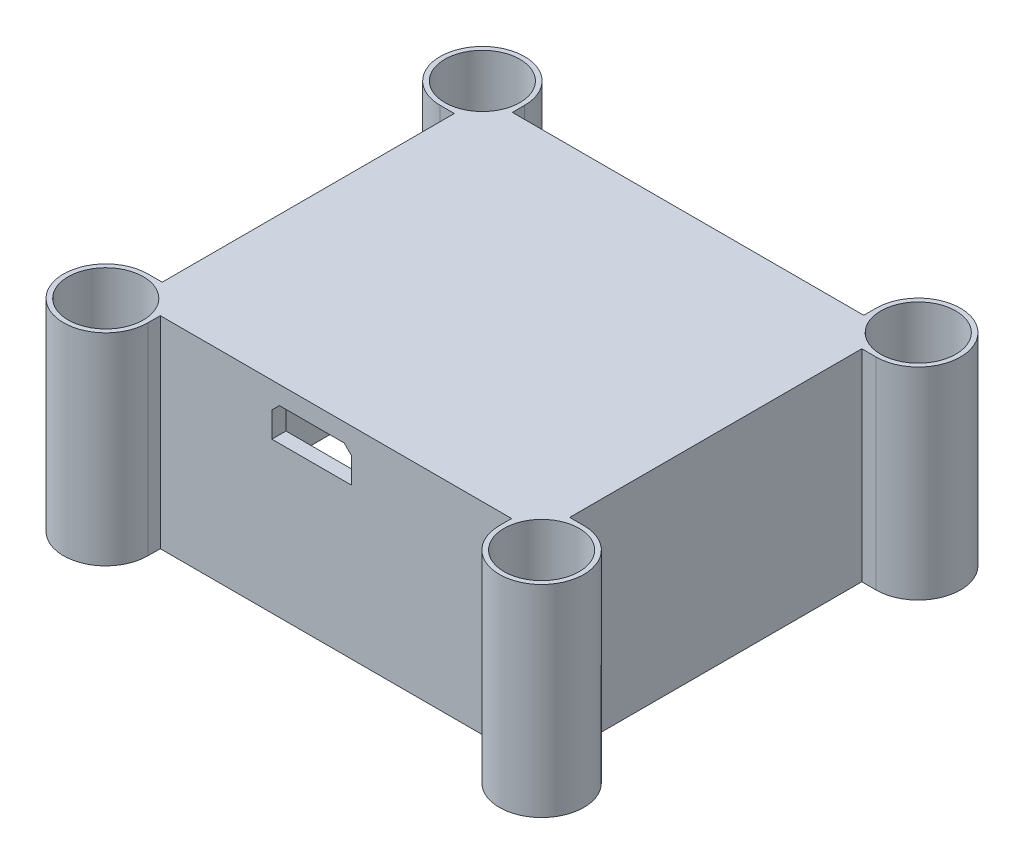
SolidWorks part; units mm, degrees
ref_plane "Front Plane" through (0, 0, 0) normal (0, 0, 1) x (1, 0, 0)
ref_plane "Top Plane" through (0, 0, 0) normal (0, 1, 0) x (1, 0, 0)
ref_plane "Right Plane" through (0, 0, 0) normal (1, 0, 0) x (0, 0, -1)
sketch "Sketch1" plane through (0, 0, 0) normal (0, 1, 0) x (1, 0, 0)
  line L0 (-20.2, 17.25) -> (-21.7, 17.25) construction
  line L1 (-20.2, 17.25) -> (20.2, 17.25)
  line L2 (-20.2, 17.25) -> (-20.2, -17.25)
  line L3 (-20.2, -17.25) -> (20.2, -17.25)
  line L4 (20.2, 17.25) -> (20.2, -17.25)
  line L5 (-20.2, 17.25) -> (20.2, -17.25) construction
  line L6 (-20.2, -17.25) -> (20.2, 17.25) construction
  line L7 (-20.2, 17.25) -> (20.2, 17.25)
  line L8 (-20.2, 17.25) -> (-20.2, 27.25)
  line L9 (-20.2, 27.25) -> (20.2, 27.25)
  line L10 (20.2, 17.25) -> (20.2, 27.25)
  line L11 (21.7, -18.75) -> (-21.7, -18.75)
  line L12 (21.7, -18.75) -> (21.7, 18.75)
  line L13 (21.7, 18.75) -> (-21.7, 18.75)
  line L14 (-21.7, -18.75) -> (-21.7, 18.75)
  line L15 (21.7, -18.75) -> (-21.7, 18.75) construction
  line L16 (21.7, 18.75) -> (-21.7, -18.75) construction
  line L17 (-20.2, 17.25) -> (-20.2, 18.75) construction
  line L18 (-23.2133, 15.5576) -> (-21.7, 15.5576)
  line L19 (-18.7133, 20.0576) -> (-18.7133, 18.75)
  line L20 (0, 18.75) -> (0, -18.75) construction
  line L21 (-21.7, 0) -> (21.7, 0) construction
  line L22 (18.7133, 20.0576) -> (18.7133, 18.75)
  line L23 (23.2133, 15.5576) -> (21.7, 15.5576)
  line L24 (18.7133, -20.0576) -> (18.7133, -18.75)
  line L25 (23.2133, -15.5576) -> (21.7, -15.5576)
  line L26 (-18.7133, -20.0576) -> (-18.7133, -18.75)
  line L27 (-23.2133, -15.5576) -> (-21.7, -15.5576)
  circle A0 centre (-23.2133, 20.0576) radius 2
  circle A1 centre (-23.2133, 20.0576) radius 4.5
  circle A2 centre (23.2133, 20.0576) radius 4.5
  circle A3 centre (23.2133, 20.0576) radius 2
  circle A4 centre (-23.2133, -20.0576) radius 2
  circle A5 centre (23.2133, -20.0576) radius 2
  circle A6 centre (23.2133, -20.0576) radius 4.5
  circle A7 centre (-23.2133, -20.0576) radius 4.5
  point P0 (0, 0)
  point P9 (0, 0)
  dimension "D5" = 4
  dimension "D6" = 9
  dimension "D1" = 40.4
  dimension "D2" = 34.5
  dimension "D3" = 10
  dimension "D4" = 1.5
extrude "Boss-Extrude1" add sketch "Sketch1" along normal blind 20 contours A7 L11 A4 L14 | L27 A7 L14 | A7 L14 L11 L3 L2 | L11 A7 L26 | L3 A7 L11 A6 | L14 A7 L2 A1 | A1 L14 A0 L13 L8 | L13 A1 L8 | L14 A1 L2 L8 L13 | L1 A1 L13 L8 | A1 L18 L14 | A1 L13 L19 | L7 A2 L13 A1 | L13 A3 L12 A2 L10 | L13 A2 L22 | A2 L1 L10 L13 | A2 L12 L13 L10 L4 | L23 A2 L12 | A6 L12 A2 L4 | A2 L13 L10 | L12 A6 L4 L3 L11 | A6 L25 L12 | A6 L12 A5 L11 | A6 L11 L24 region at (-19.6937, 0, -18.1019) region at (-20.9935, 0, -17.4625) region at (0, 0, -17.9949) region at (-20.9432, 0, 0) region at (-20.95, 0, -18.8672) region at (-19.558, 0, -20.6683) region at (19.6937, 0, -18.1019) region at (-18.7714, 0, -19.0755) region at (-20.6382, 0, 17.6373) region at (-22.0761, 0, -15.6358) region at (20.9935, 0, -17.4625) region at (19.558, 0, -20.6683) region at (18.7714, 0, -19.0755) region at (20.9432, 0, 0) region at (0, 0, 17.9949) region at (-22.0761, 0, 15.6358) region at (-21.8273, 0, 17.2848) region at (20.3172, 0, -21.0749) region at (20.6382, 0, 17.6373) region at (22.0761, 0, -15.6358) region at (-18.7714, 0, 19.0755) region at (22.4671, 0, 15.749) region at (22.0761, 0, 15.6358) region at (18.7714, 0, 19.0755)
sketch "Sketch2" plane through (0, 20, 0) normal (0, 1, 0) x (1, 0, 0)
  line L12 (-21.7, 15.5576) -> (-21.7, -15.5576)
  line L13 (-21.7, -15.5576) -> (-23.2133, -15.5576)
  line L14 (-18.7133, -20.0576) -> (-18.7133, -18.75)
  line L15 (-18.7133, -18.75) -> (18.7133, -18.75)
  line L16 (18.7133, -18.75) -> (18.7133, -20.0576)
  line L17 (23.2133, -15.5576) -> (21.7, -15.5576)
  line L18 (21.7, -15.5576) -> (21.7, 15.5576)
  line L19 (21.7, 15.5576) -> (23.2133, 15.5576)
  line L20 (18.7133, 20.0576) -> (18.7133, 18.75)
  line L21 (18.7133, 18.75) -> (-18.7133, 18.75)
  line L22 (-18.7133, 18.75) -> (-18.7133, 20.0576)
  line L23 (-23.2133, 15.5576) -> (-21.7, 15.5576)
  line L24 (-21.7, 15.5576) -> (-21.7, -15.5576)
  line L25 (-21.7, -15.5576) -> (-23.2133, -15.5576)
  line L26 (-18.7133, -20.0576) -> (-18.7133, -18.75)
  line L27 (-18.7133, -18.75) -> (18.7133, -18.75)
  line L28 (18.7133, -18.75) -> (18.7133, -20.0576)
  line L29 (23.2133, -15.5576) -> (21.7, -15.5576)
  line L30 (21.7, -15.5576) -> (21.7, 15.5576)
  line L31 (21.7, 15.5576) -> (23.2133, 15.5576)
  line L32 (18.7133, 20.0576) -> (18.7133, 18.75)
  line L33 (18.7133, 18.75) -> (-18.7133, 18.75)
  line L34 (-18.7133, 18.75) -> (-18.7133, 20.0576)
  line L35 (-23.2133, 15.5576) -> (-21.7, 15.5576)
  circle A0 centre (23.2133, -20.0576) radius 2 construction
  circle A1 centre (23.2133, 20.0576) radius 2 construction
  circle A2 centre (-23.2133, 20.0576) radius 2 construction
  circle A3 centre (-23.2133, -20.0576) radius 2 construction
  arc A4 (-23.2133, -15.5576) -> (-18.7133, -20.0576) centre (-23.2133, -20.0576) ccw
  arc A5 (18.7133, -20.0576) -> (23.2133, -15.5576) centre (23.2133, -20.0576) ccw
  arc A6 (23.2133, 15.5576) -> (18.7133, 20.0576) centre (23.2133, 20.0576) ccw
  arc A7 (-18.7133, 20.0576) -> (-23.2133, 15.5576) centre (-23.2133, 20.0576) ccw
  arc A8 (-23.2133, -15.5576) -> (-18.7133, -20.0576) centre (-23.2133, -20.0576) ccw
  arc A9 (18.7133, -20.0576) -> (23.2133, -15.5576) centre (23.2133, -20.0576) ccw
  arc A10 (23.2133, 15.5576) -> (18.7133, 20.0576) centre (23.2133, 20.0576) ccw
  arc A11 (-18.7133, 20.0576) -> (-23.2133, 15.5576) centre (-23.2133, 20.0576) ccw
  circle A12 centre (23.2133, -20.0576) radius 2
  circle A13 centre (23.2133, 20.0576) radius 2
  circle A14 centre (-23.2133, 20.0576) radius 2
  circle A15 centre (-23.2133, -20.0576) radius 2
  dimension "D1" = 0
extrude "Boss-Extrude2" add sketch "Sketch2" along normal blind 1.5
sketch "Sketch3" plane through (0, 21.5, 0) normal (0, 1, 0) x (1, 0, 0)
  circle A0 centre (-23.2133, -20.0576) radius 4
  arc A1 (-23.2133, -15.5576) -> (-18.7133, -20.0576) centre (-23.2133, -20.0576) ccw construction
  circle A2 centre (-23.2133, 20.0576) radius 4
  circle A3 centre (23.2133, 20.0576) radius 4
  circle A4 centre (23.2133, -20.0576) radius 4
  dimension "D1" = 0.5
extrude "Cut-Extrude1" cut sketch "Sketch3" against normal offset from surface (20 mm away) 1.5 up to face at (0, 0, 0)
sketch "Sketch4" plane through (0, 20, 0) normal (0, -1, 0) x (1, 0, 0)
  line L0 (-20.2, 17.25) -> (20.2, 17.25) construction
  line L1 (-7.2, 17.25) -> (2.05, 17.25)
  line L2 (-7.2, 17.25) -> (-7.2, 13.25)
  line L3 (-7.2, 13.25) -> (2.05, 13.25)
  line L4 (2.05, 17.25) -> (2.05, 13.25)
  line L5 (-7.2, 13.25) -> (-20.2, 13.25)
  line L6 (-20.2, -17.25) -> (-20.2, 17.25) construction
  line L7 (2.05, 13.25) -> (20.2, 13.25)
  line L8 (20.2, 17.25) -> (20.2, -17.25) construction
  line L9 (-20.2, -17.25) -> (-20.2, 17.25) construction
  line L10 (-20.2, -17.25) -> (20.2, -17.25) construction
  line L11 (-20.2, -17.25) -> (-15.9, -17.25)
  line L12 (-20.2, -17.25) -> (-20.2, -12.95)
  line L13 (-20.2, -12.95) -> (-15.9, -12.95)
  line L14 (-15.9, -17.25) -> (-15.9, -12.95)
  line L15 (14.7, -17.25) -> (11.7, -17.25)
  line L16 (14.7, -17.25) -> (14.7, -15.25)
  line L17 (14.7, -15.25) -> (11.7, -15.25)
  line L18 (11.7, -17.25) -> (11.7, -15.25)
  line L19 (20.2, 17.25) -> (20.2, -17.25) construction
  point P14 (-7.2, 15.25)
  line M5 (20.2, 17.25) -> (-20.2, 17.25)
  line M6 (-20.2, 17.25) -> (-20.2, -17.25)
  line M7 (-20.2, -17.25) -> (20.2, -17.25)
  line M8 (20.2, -17.25) -> (20.2, 17.25)
  dimension "D1" = 9.25
  dimension "D2" = 4
  dimension "D3" = 13
  dimension "D4" = 4.3
  dimension "D5" = 5.5
  dimension "D6" = 3
  dimension "D7" = 2
extrude "Boss-Extrude3" add sketch "Sketch4" along normal blind 1.1 contours L5 L2 M5 M6 | L14 L13 M7 M6 | L4 L7 M8 M5 | L18 L16 L17 M7 region at (-13.7, 20, 15.25) region at (11.125, 20, 15.25) region at (-18.05, 20, -15.1) region at (13.2, 20, -16.25)
sketch "Sketch5" plane through (0, 18.9, 0) normal (0, -1, 0) x (1, 0, 0)
  line L1 (-16.55, -17.25) -> (-19.55, -17.25)
  line L2 (-16.55, -17.25) -> (-16.55, -12.45)
  line L3 (-16.55, -12.45) -> (-19.55, -12.45)
  line L4 (-19.55, -17.25) -> (-19.55, -12.45)
  line L5 (-20.2, -12.95) -> (-15.9, -12.95) construction
  line L6 (11.7, -17.25) -> (11.7, -15.25) construction
  line L7 (14.7, -17.25) -> (11.7, -17.25)
  line L8 (14.7, -17.25) -> (14.7, -14.75)
  line L9 (14.7, -14.75) -> (11.7, -14.75)
  line L10 (11.7, -17.25) -> (11.7, -14.75)
  line L11 (-18.05, -12.45) -> (-18.05, -12.95) construction
  line L12 (13.2, -14.75) -> (13.2, -15.25) construction
  line L13 (14.7, -15.25) -> (11.7, -15.25) construction
  line L14 (-13.7, 17.25) -> (-13.7, 13.25) construction
  line L15 (-7.2, 17.25) -> (-20.2, 17.25) construction
  line L16 (-7.2, 13.25) -> (-20.2, 13.25) construction
  line L17 (-20.2, 17.25) -> (20.2, 17.25) construction
  line L18 (-15.2, 17.25) -> (-12.2, 17.25)
  line L19 (-15.2, 17.25) -> (-15.2, 12.75)
  line L20 (-15.2, 12.75) -> (-12.2, 12.75)
  line L21 (-12.2, 17.25) -> (-12.2, 12.75)
  line L22 (-15.2, 17.25) -> (-12.2, 12.75) construction
  line L23 (-15.2, 12.75) -> (-12.2, 17.25) construction
  line L24 (-13.7, 13.25) -> (-13.7, 12.75) construction
  line L25 (11.125, 17.25) -> (11.125, 13.25) construction
  line L26 (20.2, 17.25) -> (2.05, 17.25) construction
  line L27 (2.05, 13.25) -> (20.2, 13.25) construction
  line L28 (11.125, 13.25) -> (11.125, 12.75) construction
  line L29 (9.625, 17.25) -> (12.625, 17.25)
  line L30 (9.625, 17.25) -> (9.625, 12.75)
  line L31 (9.625, 12.75) -> (12.625, 12.75)
  line L32 (12.625, 17.25) -> (12.625, 12.75)
  line L33 (9.625, 17.25) -> (12.625, 12.75) construction
  line L34 (9.625, 12.75) -> (12.625, 17.25) construction
  line L35 (-20.2, -17.25) -> (-15.9, -17.25) construction
  point P5 (0, 0)
  point P6 (-20.2, -12.45)
  point P28 (-13.7, 15)
  point P42 (11.125, 15)
  point P47 (0, 0)
  point P49 (0, 0)
  point P50 (0, 0)
  dimension "D1" = 0.5
  dimension "D2" = 3
extrude "Boss-Extrude4" add sketch "Sketch5" along normal blind 1
chamfer "Chamfer1" distance 0.5 angle 45 2 edges at (-18.05, 17.9, -12.45) (13.2, 17.9, -14.75)
sketch "Sketch6" plane through (0, 0, 17.25) normal (0, 0, -1) x (-1, 0, 0)
  line L0 (7.2, 20) -> (-2.05, 20) construction
  line L1 (2.575, 20) -> (2.575, 0) construction
  line L2 (20.2, 0) -> (-20.2, 0) construction
  line L4 (-1.675, 16.05) -> (6.825, 16.05)
  line L5 (-1.675, 16.05) -> (-1.675, 19.55)
  line L6 (-1.675, 19.55) -> (6.825, 19.55)
  line L7 (6.825, 16.05) -> (6.825, 19.55)
  line L8 (-1.675, 16.05) -> (6.825, 19.55) construction
  line L9 (-1.675, 19.55) -> (6.825, 16.05) construction
  point P6 (2.575, 17.8)
  dimension "D1" = 8.5
  dimension "D2" = 3.5
  dimension "D3" = 3.95
extrude "Cut-Extrude2" cut sketch "Sketch6" against normal up to next
chamfer "Chamfer2" distance 0.8 angle 45 2 edges at (-6.825, 19.55, 18) (1.675, 19.55, 18)
